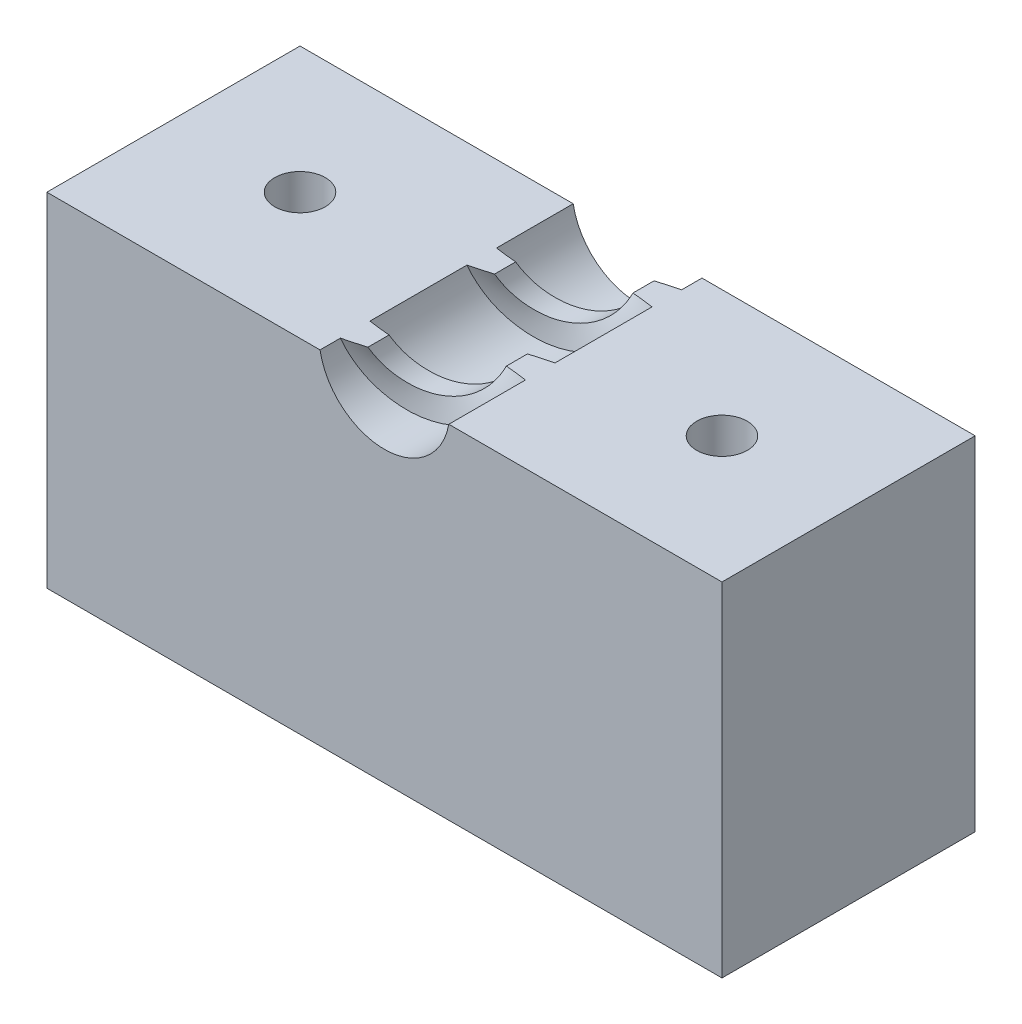
SolidWorks part; units mm, degrees
ref_plane "前视基准面" through (0, 0, 0) normal (0, 0, 1) x (1, 0, 0)
ref_plane "上视基准面" through (0, 0, 0) normal (0, 1, 0) x (1, 0, 0)
ref_plane "右视基准面" through (0, 0, 0) normal (1, 0, 0) x (0, 0, -1)
other "Configuration Table"
sketch "草图1" plane through (0, 0, 0) normal (0, 0, 1) x (1, 0, 0)
  line L1 (-8, -8) -> (8, -8)
  line L2 (-8, -8) -> (-8, 8)
  line L3 (-8, 8) -> (8, 8)
  line L4 (8, -8) -> (8, 8)
  line L5 (-8, -8) -> (8, 8) construction
  line L6 (-8, 8) -> (8, -8) construction
  circle A0 centre (0, 0) radius 1.55
  point P0 (0, 0)
  dimension "D3" = 3.1
  dimension "D1" = 16
  dimension "D2" = 16
extrude "凸台-拉伸1" add sketch "草图1" along normal mid plane 6
sketch "草图9" plane through (0, 0, 3) normal (0, 0, 1) x (1, 0, 0)
  circle A0 centre (0, 0) radius 1.55 construction
  circle A1 centre (0, 0) radius 1.55
curve "螺旋线/涡状线1" pitch 3 height 6 turns 2
sketch "草图10" plane through (0, 0, 0) normal (0, 1, 0) x (1, 0, 0)
  line L0 (1.55, 2.6) -> (1.55, 1.9)
  line L1 (1.55, 1.9) -> (1.05, 2)
  line L2 (1.05, 2) -> (1.05, 2.5)
  line L3 (1.05, 2.5) -> (1.55, 2.6)
  line L5 (-0.1616, 2.25) -> (2.6454, 2.25) construction
  line L7 (8, 3) -> (-8, 3) construction
  line L8 (1.55, 3) -> (-1.55, 3) construction
  line L9 (1.55, 3) -> (-1.55, 3) construction
  dimension "D1" = 0.7
  dimension "D2" = 0.5
  dimension "D3" = 0.5
  dimension "D4" = 0.75
sweep "扫描1" add profiles "草图10" path "螺旋线/涡状线1"
sketch "草图7" plane through (0, 0, 0) normal (0, 0, 1) x (1, 0, 0)
  line L0 (0, 0) -> (-1.0142, -0.2718)
  line L1 (0, 0) -> (1.0142, -0.2718)
  line L2 (-1.0142, -0.2718) -> (-8, -0.2718)
  line L3 (1.0142, -0.2718) -> (8, -0.2718)
  line L6 (8, -8) -> (8, 8)
  line L7 (-8, -8) -> (8, -8)
  line L8 (-8, 8) -> (-8, -8)
  line L9 (8, 8) -> (-8, 8)
  line L10 (8, -8) -> (8, 8)
  line L11 (-8, -8) -> (8, -8)
  line L12 (-8, 8) -> (-8, -8)
  line L13 (8, 8) -> (-8, 8)
  circle A0 centre (0, 0) radius 1.05
  dimension "D1" = 2.1
  dimension "D2" = 0
  dimension "D3" = 150
extrude "切除-拉伸2" cut sketch "草图7" against normal through all both and the other way through all contours A0 L3 L10 L13 L12 L2 | L1 A0 L0 | L0 A0 L1
sketch "草图8" plane through (0, 0, 0) normal (0, 1, 0) x (1, 0, 0)
  line L0 (0, 5.5834) -> (0, -5.0797) construction
  circle A0 centre (-5, 0) radius 0.6
  circle A1 centre (5, 0) radius 0.6
  dimension "D2" = 1.2
  dimension "D3" = 10
extrude "切除-拉伸3" cut sketch "草图8" against normal through all
sketch "草图11" plane through (0, -8, 0) normal (0, -1, 0) x (1, 0, 0)
  line L4 (-8, -3) -> (8, -3)
  line L5 (8, -3) -> (8, 3)
  line L6 (8, 3) -> (-8, 3)
  line L7 (-8, 3) -> (-8, -3)
  line L8 (-8, -3) -> (8, -3)
  line L9 (8, -3) -> (8, 3)
  line L10 (8, 3) -> (-8, 3)
  line L11 (-8, 3) -> (-8, -3)
  circle A0 centre (5, 0) radius 0.6 construction
  circle A1 centre (-5, 0) radius 0.6 construction
  circle A2 centre (5, 0) radius 0.6
  circle A3 centre (-5, 0) radius 0.6
  dimension "D1" = 0
extrude "凸台-拉伸2" add sketch "草图11" along normal blind 0.4
equation "\"x\"=0.8094"
